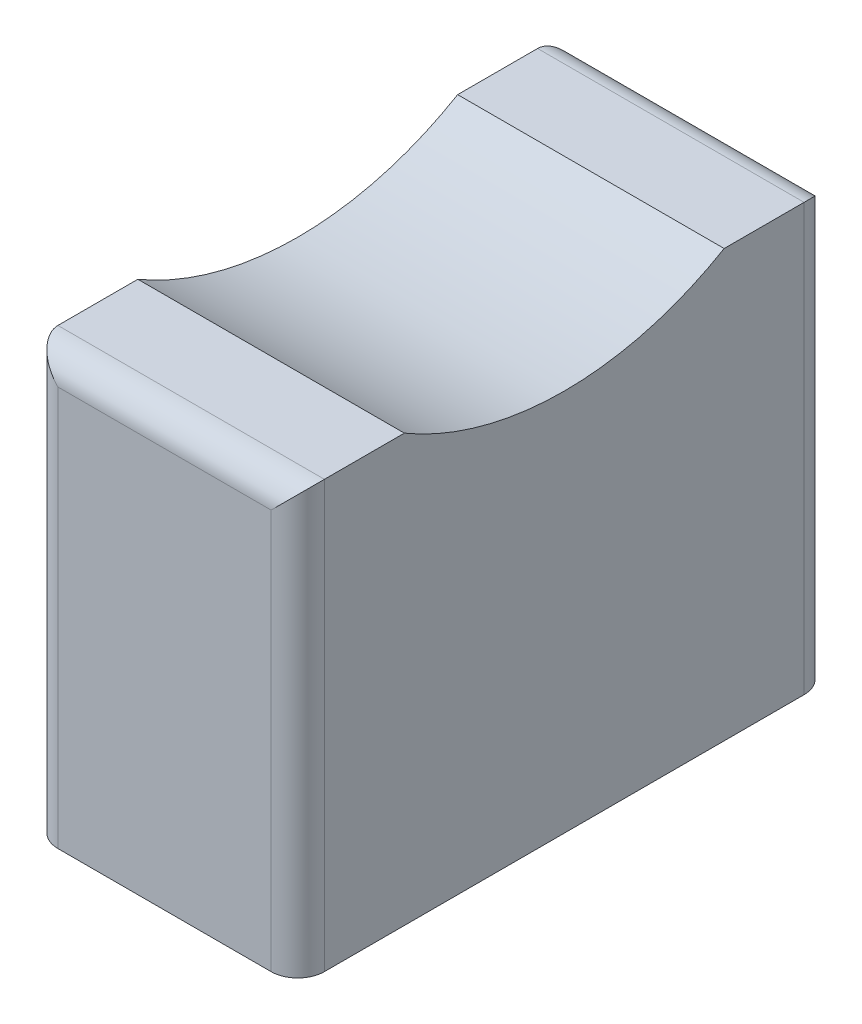
SolidWorks part; units mm, degrees
ref_plane "Front Plane" through (0, 0, 0) normal (0, 0, 1) x (1, 0, 0)
ref_plane "Top Plane" through (0, 0, 0) normal (0, 1, 0) x (1, 0, 0)
ref_plane "Right Plane" through (0, 0, 0) normal (1, 0, 0) x (0, 0, -1)
sketch "Sketch1" plane through (0, 0, 0) normal (0, 1, 0) x (1, 0, 0)
  line L1 (-5, -10) -> (5, -10)
  line L2 (-5, -10) -> (-5, 10)
  line L3 (-5, 10) -> (5, 10)
  line L4 (5, -10) -> (5, 10)
  line L5 (-5, -10) -> (5, 10) construction
  line L6 (-5, 10) -> (5, -10) construction
  point P0 (0, 0)
  dimension "D1" = 20
  dimension "D2" = 10
extrude "Boss-Extrude1" add sketch "Sketch1" along normal blind 16
sketch "Sketch2" plane through (0, 0, 0) normal (0, -1, 0) x (1, 0, 0)
  line L0 (5, 0) -> (-5, 0) construction
  line L1 (5, 10) -> (5, -10) construction
  line L2 (-5, -10) -> (-5, 10) construction
  line L4 (-0.5, 2) -> (0.5, 2)
  line L5 (-0.5, 2) -> (-0.5, -2)
  line L6 (-0.5, -2) -> (0.5, -2)
  line L7 (0.5, 2) -> (0.5, -2)
  line L8 (-0.5, 2) -> (0.5, -2) construction
  line L9 (-0.5, -2) -> (0.5, 2) construction
  point P6 (0, 0)
  dimension "D1" = 4
  dimension "D2" = 1
extrude "Cut-Extrude1" cut sketch "Sketch2" against normal blind 7
sketch "Sketch6" plane through (5, 0, 0) normal (1, 0, 0) x (0, 0, -1)
  line L0 (-10, 16) -> (10, 16) construction
  line L1 (-10, 16) -> (-10, 0) construction
  line L2 (10, 16) -> (10, 0) construction
  line L3 (-6, 16) -> (6, 16)
  arc A0 (-6, 16) -> (6, 16) centre (0, 26.1988) ccw
  dimension "D1" = 4
  dimension "D2" = 4
extrude "Cut-Extrude2" cut sketch "Sketch6" against normal blind 10
fillet "Fillet2" radius 1 6 edges at (0, 16, -10) (-5, 8, -10) (5, 8, -10) (-5, 8, 10) (5, 8, 10) (0, 16, 10)
